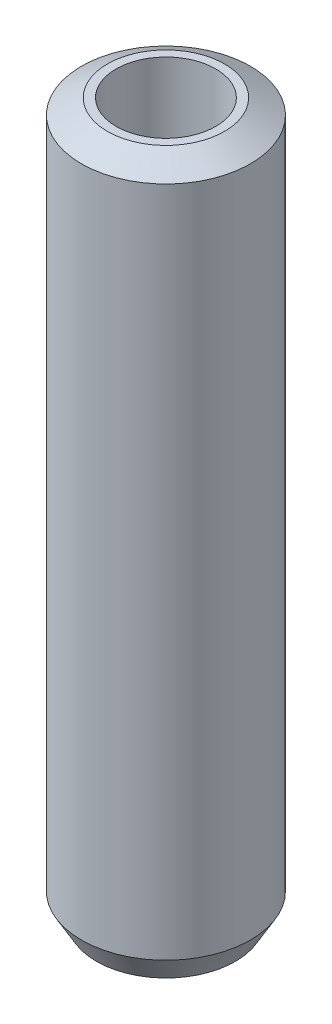
SolidWorks part; units mm, degrees
ref_plane "Front Plane" through (0, 0, 0) normal (0, 0, 1) x (1, 0, 0)
ref_plane "Top Plane" through (0, 0, 0) normal (0, 1, 0) x (1, 0, 0)
ref_plane "Right Plane" through (0, 0, 0) normal (1, 0, 0) x (0, 0, -1)
sketch "Sketch1" plane through (0, 0, 0) normal (0, 1, 0) x (1, 0, 0)
  circle A0 centre (0, 0) radius 20
  dimension "SHAFT_OD" = 40
extrude "Boss-Extrude1" add sketch "Sketch1" along normal blind 168.7666
sketch "Sketch2" plane through (0, 0, 0) normal (0, 1, 0) x (1, 0, 0)
  circle A0 centre (0, 0) radius 11.7913
  dimension "BORE_D" = 23.5825
extrude "Cut-Extrude1" cut sketch "Sketch2" along normal through all
chamfer "Chamfer1" distance 3.5539 angle 60 2 edges at (0, 168.7666, 20) (0, 0, 20) first distance on face at (0, 168.7666, 20) first distance on face at (0, 0, 11.7913)
